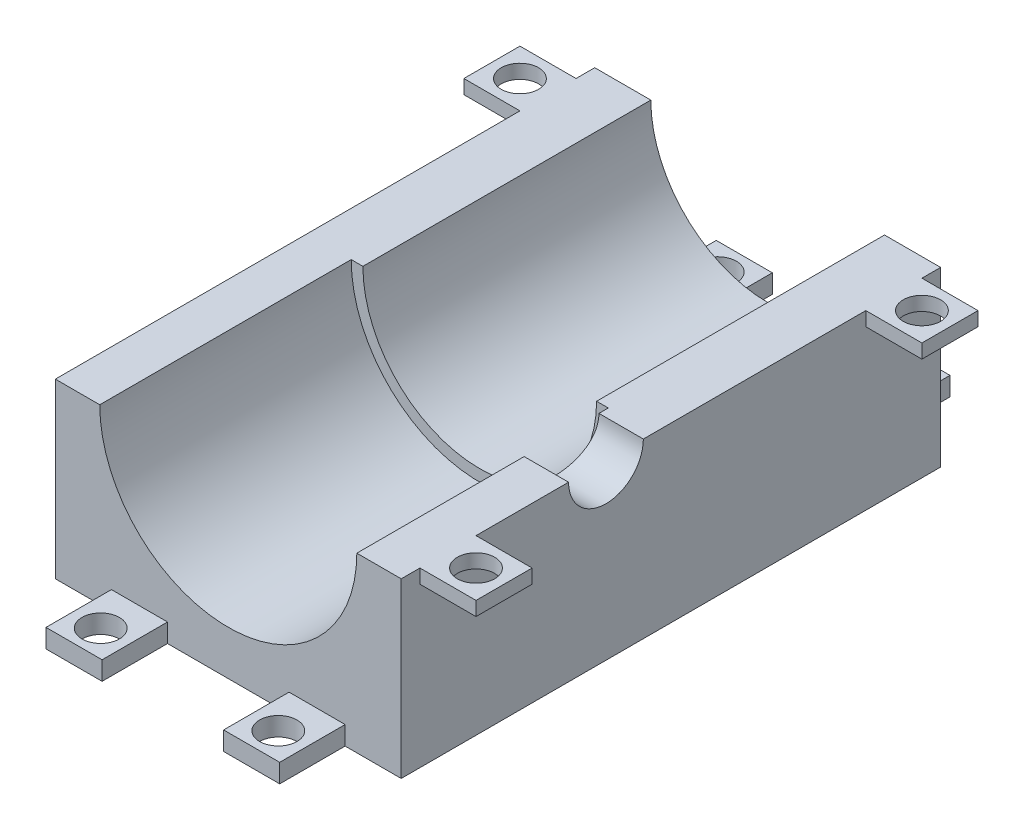
SolidWorks part; units mm, degrees
note: The reader was unsure of these and kept them because the rebuilt part matched: shared geometry of "스케치8<3>".
ref_plane "정면도" through (0, 0, 0) normal (0, 0, 1) x (1, 0, 0)
ref_plane "평면도" through (0, 0, 0) normal (0, 1, 0) x (1, 0, 0)
ref_plane "우측면도" through (0, 0, 0) normal (1, 0, 0) x (0, 0, -1)
sketch "스케치1" plane through (0, 0, 0) normal (0, 0, 1) x (1, 0, 0)
  line L0 (-13.5, 0) -> (-18.5, 0)
  line L1 (-18.5, 0) -> (-18.5, -18.5)
  line L2 (-18.5, -18.5) -> (18.5, -18.5)
  line L3 (18.5, -18.5) -> (18.5, 0)
  line L4 (18.5, 0) -> (13.5, 0)
  arc A0 (-13.5, 0) -> (13.5, 0) centre (0, 0) ccw
  arc A1 (-16, 0) -> (16, 0) centre (0, 0) ccw construction
  circle A2 centre (0, 0) radius 11.5
  point P9 (0, -16)
  dimension "D1" = 27
  dimension "D2" = 32
  dimension "D6" = 23
  dimension "D3" = 5
  dimension "D4" = 5
  dimension "D5" = 2.5
extrude "보스-돌출1" add sketch "스케치1" against normal blind 57.7 contours L1 L2 L3 L4 A0 L0
ref_plane "평면1" through (0, 0, -26.9) normal (0, 0, 1) x (1, 0, 0)
sketch "스케치3" plane through (0, 0, -26.9) normal (0, 0, 1) x (1, 0, 0)
  line L0 (-13.5, 0) -> (-11.5, 0)
  line L1 (13.5, 0) -> (11.5, 0)
  circle A0 centre (0, 0) radius 11.5 construction
  arc A1 (-11.5, 0) -> (11.5, 0) centre (0, 0) ccw
  arc A2 (-13.5, 0) -> (13.5, 0) centre (0, 0) ccw construction
  arc A3 (-13.5, 0) -> (13.5, 0) centre (0, 0) ccw
extrude "보스-돌출2" add sketch "스케치3" against normal blind 30.8
sketch "스케치5" plane through (18.5, 0, 0) normal (-1, 0, 0) x (0, 0, 1)
  line L0 (-57.7, 0) -> (0, 0) construction
  line L1 (0, 0) -> (0, -18.5) construction
  circle A0 centre (-21.9, 0) radius 4
  dimension "D2" = 8
  dimension "D1" = 21.9
extrude "컷-돌출1" cut sketch "스케치5" along normal blind 15
sketch "스케치7" plane through (0, -18.5, 0) normal (0, -1, 0) x (1, 0, 0)
  line L23 (-18.5, 0) -> (18.5, 0) construction
  line L24 (6.5, 7) -> (12.5, 7)
  line L30 (6.5, 7) -> (6.5, 0)
  line L31 (6.5, 0) -> (12.5, 0)
  line L36 (12.5, 7) -> (12.5, 0)
  line L37 (6.5, 0) -> (12.5, 7) construction
  line L43 (-12.5, 7) -> (-6.5, 7)
  line L44 (-12.5, 7) -> (-12.5, 0)
  line L45 (-12.5, 0) -> (-6.5, 0)
  line L46 (-6.5, 7) -> (-6.5, 0)
  line L47 (12.5, 0) -> (6.5, 7) construction
  line L48 (18.5, -57.7) -> (18.5, 0) construction
  line L50 (-12.5, 0) -> (-6.5, 7) construction
  line L51 (-6.5, 0) -> (-12.5, 7) construction
  circle A0 centre (9.5, 4.15) radius 2
  circle A1 centre (-9.5, 4.15) radius 2
  point P10 (9.5, 3.5)
  point P14 (-9.5, 7)
  point P20 (-9.5, 3.5)
  dimension "D7" = 4
  dimension "D8" = 4
  dimension "D1" = 9
  dimension "D2" = 7
  dimension "D3" = 19
  dimension "D4" = 7
  dimension "D5" = 6
  dimension "D6" = 6
  dimension "D9" = 0.65
  dimension "D10" = 0.65
extrude "보스-돌출3" add sketch "스케치7" against normal blind 2
ref_plane "평면2" through (0, 0, -28.85) normal (0, 0, 1) x (1, 0, 0)
mirror "대칭 복사1" about plane through (0, 0, -28.85) normal (0, 0, 1) of "보스-돌출3"
sketch "스케치8" plane through (-18.5, 0, 0) normal (-1, 0, 0) x (0, 0, 1)
  line L0 (-57.7, 0) -> (0, 0) construction
  line L1 (-49.7, -1.5) -> (-55.7, -1.5)
  line L2 (-49.7, -1.5) -> (-49.7, 1.5)
  line L3 (-49.7, 1.5) -> (-55.7, 1.5)
  line L4 (-55.7, -1.5) -> (-55.7, 1.5)
  line L5 (-52.7, 1.5) -> (-52.7, -1.5) construction
  line L6 (-49.7, 0) -> (-55.7, 0) construction
  line L7 (0, 0) -> (0, -18.5) construction
  line L8 (-8, -1.5) -> (-2, -1.5)
  line L9 (-8, -1.5) -> (-8, 1.5)
  line L10 (-8, 1.5) -> (-2, 1.5)
  line L11 (-2, -1.5) -> (-2, 1.5)
  line L12 (-5, 1.5) -> (-5, -1.5) construction
  line L13 (-8, 0) -> (-2, 0) construction
  line L14 (-57.7, 0) -> (-57.7, -18.5) construction
  line L15 (-55.7, 0) -> (-49.7, 0)
  line L16 (-8, 0) -> (-2, 0)
  point P0 (-52.7, 0)
  point P6 (-5, 0)
  line M6 (0, 0) -> (-57.7, 0)
  dimension "D1" = 5
  dimension "D2" = 5
  dimension "D3" = 6
  dimension "D4" = 3
  dimension "D5" = 6
  dimension "D6" = 3
extrude "보스-돌출4" add sketch "스케치8" along normal blind 6 contours L8 L11 L9 M6 | L4 L1 L2 M6
extrude "보스-돌출5" add sketch "스케치8<3>" against normal blind 6 from surface at -37 contours L8 L11 L9 M6 | L4 L1 L2 M6 starting at face at (18.5, -6.8333, -26.5333)
sketch "스케치8<3>" plane through (-18.5, 0, 0) normal (-1, 0, 0) x (0, 0, 1) same geometry as "스케치8"
sketch "스케치9" plane through (0, 0, 0) normal (0, 1, 0) x (1, 0, 0)
  line L0 (-18.5, 55.7) -> (-24.5, 49.7) construction
  line L1 (-24.5, 55.7) -> (-18.5, 49.7) construction
  line L2 (-18.5, 8) -> (-24.5, 2) construction
  line L3 (-24.5, 8) -> (-18.5, 2) construction
  line L4 (0, 0) -> (0, 57.7) construction
  line L5 (11.5, 57.7) -> (-11.5, 57.7) construction
  circle A0 centre (-21.5, 52.7) radius 2
  circle A1 centre (-21.5, 5) radius 2
  circle A2 centre (21.5, 5) radius 2
  circle A3 centre (21.5, 52.7) radius 2
  dimension "D1" = 4
extrude "컷-돌출2" cut sketch "스케치9" against normal blind 6
sketch "스케치10" plane through (0, 0, 0) normal (0, 0, 1) x (1, 0, 0)
  line L0 (-13.5, 0) -> (-13.75, 0)
  line L1 (13.5, 0) -> (13.75, 0)
  arc A0 (-13.75, 0) -> (13.75, 0) centre (0, 0) ccw
  arc A1 (-13.5, 0) -> (13.5, 0) centre (0, 0) ccw construction
  arc A2 (-13.5, 0) -> (13.5, 0) centre (0, 0) ccw
  dimension "D1" = 0.25
extrude "컷-돌출3" cut sketch "스케치10" against normal up to surface (26.9 mm away)
sketch "스케치11" plane through (0, 0, -26.9) normal (0, 0, 1) x (1, 0, 0)
  line L2 (-11.5, 0) -> (-13.75, 0) construction
  line L3 (13.75, 0) -> (11.5, 0) construction
  line L4 (-11.5, 0) -> (-12.5, 0)
  line L5 (12.5, 0) -> (11.5, 0)
  arc A3 (-12.5, 0) -> (12.5, 0) centre (0, 0) ccw
  dimension "D2" = 25
extrude "컷-돌출4" cut sketch "스케치11" against normal through all
sketch "스케치12" plane through (0, 0, 0) normal (0, 1, 0) x (1, 0, 0)
  line L2 (-24.5, 8) -> (-18.5, 8)
  line L3 (-24.5, 8) -> (-24.5, 2)
  line L4 (-24.5, 2) -> (-18.5, 2)
  line L5 (-18.5, 8) -> (-18.5, 2)
extrude "컷-돌출5" cut sketch "스케치12" against normal blind 10
